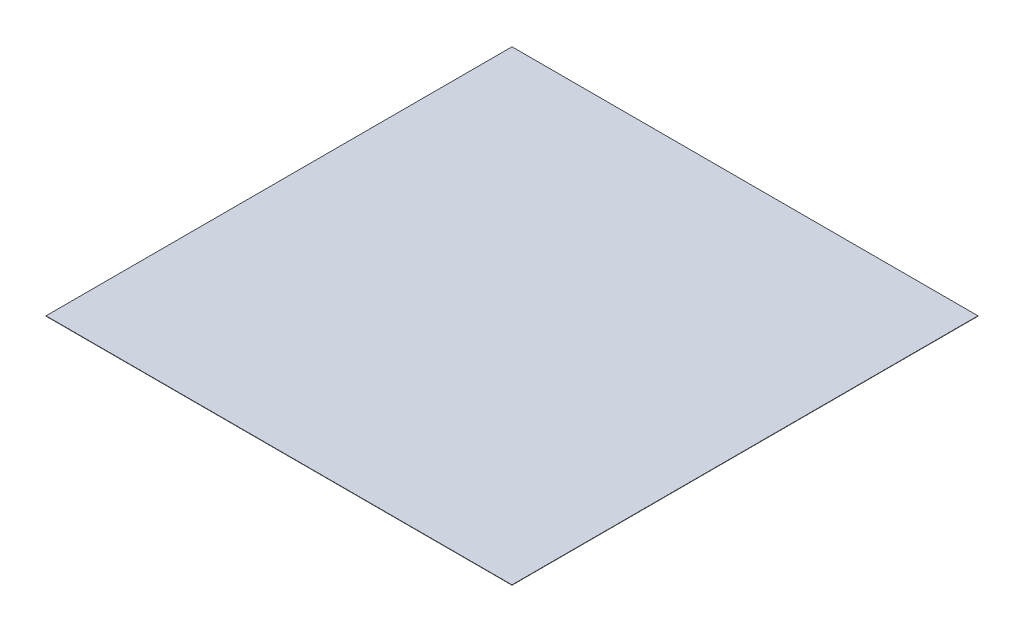
SolidWorks part; units mm, degrees
material "3.0205 (EN-AW 1200)"
ref_plane "Front Plane" through (0, 0, 0) normal (0, 0, 1) x (1, 0, 0)
ref_plane "Top Plane" through (0, 0, 0) normal (0, 1, 0) x (1, 0, 0)
ref_plane "Right Plane" through (0, 0, 0) normal (1, 0, 0) x (0, 0, -1)
sketch "Sketch1" plane through (0, 0, 0) normal (0, 1, 0) x (1, 0, 0)
  line L1 (0, 0) -> (1500, 0)
  line L2 (0, 0) -> (0, 1500)
  line L3 (0, 1500) -> (1500, 1500)
  line L4 (1500, 0) -> (1500, 1500)
extrude "Boss-Extrude1" add sketch "Sketch1" along normal blind 1
